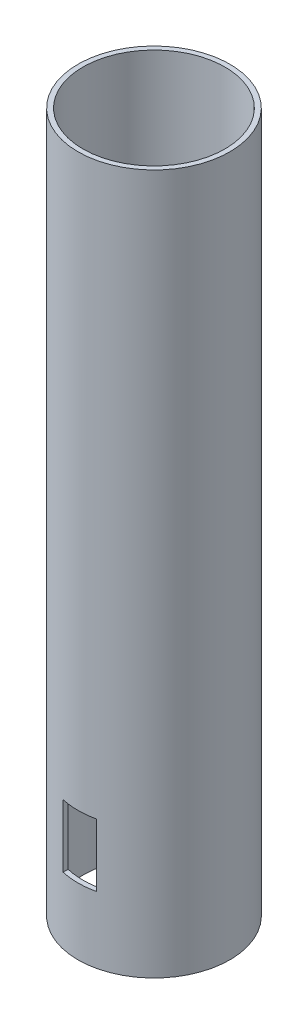
SolidWorks part; units mm, degrees
ref_plane "Front Plane" through (0, 0, 0) normal (0, 0, 1) x (1, 0, 0)
ref_plane "Top Plane" through (0, 0, 0) normal (0, 1, 0) x (1, 0, 0)
ref_plane "Right Plane" through (0, 0, 0) normal (1, 0, 0) x (0, 0, -1)
sketch "Sketch1" plane through (0, 0, 0) normal (0, 1, 0) x (1, 0, 0)
  circle A0 centre (0, 0) radius 27.125
  circle A1 centre (0, 0) radius 25.375
  dimension "Outer_Dia" = 54.25
  dimension "Inner_Dia" = 50.75
extrude "Boss-Extrude1" add sketch "Sketch1" along normal mid plane 250
sketch "Sketch3" plane through (0, 0, 0) normal (0, 0, 1) x (1, 0, 0)
  line L0 (-27.125, -125) -> (27.125, -125) construction
  line L1 (1, -65) -> (-1, -65)
  line L2 (1, -65) -> (1, -125)
  line L3 (1, -125) -> (-1, -125)
  line L4 (-1, -65) -> (-1, -125)
  line L5 (1, -65) -> (-1, -125) construction
  line L6 (1, -125) -> (-1, -65) construction
  point P0 (0, -95)
  dimension "D1" = 2
  dimension "D2" = 60
curve "Curve1"
sketch "Sketch4" plane through (0, 0, 0) normal (1, 0, 0) x (0, 0, -1)
  line L0 (-27.125, -125) -> (27.125, -125) construction
  line L1 (1, -65) -> (-1, -65)
  line L2 (1, -65) -> (1, -125)
  line L3 (1, -125) -> (-1, -125)
  line L4 (-1, -65) -> (-1, -125)
  line L5 (1, -65) -> (-1, -125) construction
  line L6 (1, -125) -> (-1, -65) construction
  point P0 (0, -95)
  dimension "D1" = 60
  dimension "D2" = 2
curve "Curve2"
sketch "Sketch5" plane through (0, 0, 0) normal (0, 0, 1) x (1, 0, 0)
  line L0 (-63.3621, -95) -> (63.3621, -95) construction
  line L1 (-27.125, -125) -> (27.125, -125) construction
  line L3 (-6, -101.2) -> (6, -101.2)
  line L4 (-6, -101.2) -> (-6, -78.75)
  line L5 (-6, -78.75) -> (6, -78.75)
  line L6 (6, -101.2) -> (6, -78.75)
  point P4 (0, -95)
  point P10 (0, -101.2)
  dimension "D1" = 30
  dimension "D2" = 6.2
  dimension "D3" = 22.45
  dimension "D4" = 12
extrude "Cut-Extrude1" cut sketch "Sketch5" against normal through all both and the other way through all
